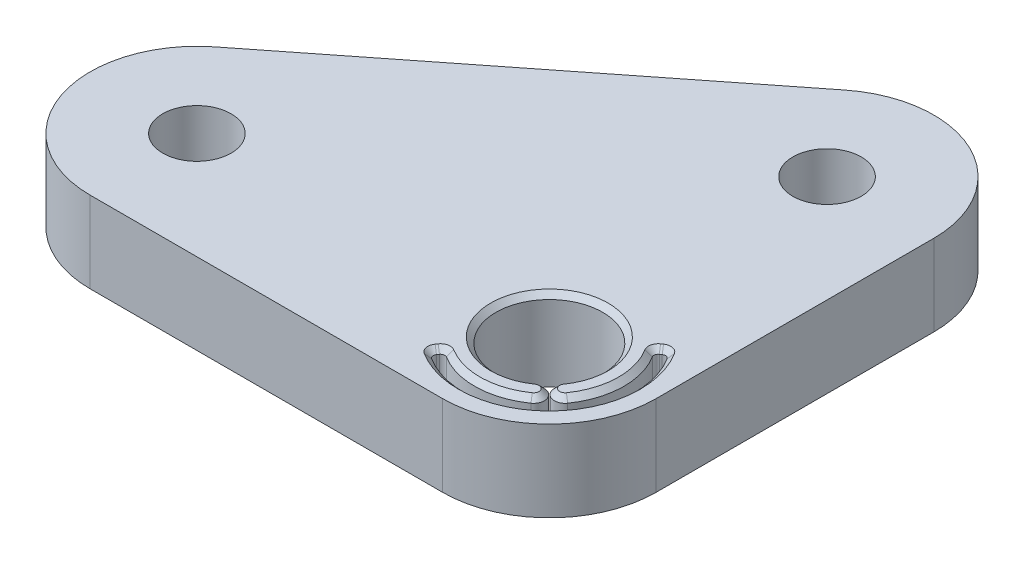
SolidWorks part; units mm, degrees
ref_plane "Front" through (0, 0, 0) normal (0, 0, 1) x (1, 0, 0)
ref_plane "Top" through (0, 0, 0) normal (0, 1, 0) x (1, 0, 0)
ref_plane "Right" through (0, 0, 0) normal (1, 0, 0) x (0, 0, -1)
sketch "Sketch1" plane through (0, 0, 0) normal (0, 1, 0) x (1, 0, 0)
  line L0 (0, 0) -> (16.5, 0) construction
  line L1 (16.5, 0) -> (0, 13) construction
  line L2 (0, 13) -> (0, 0) construction
  line L3 (-5, -5) -> (30.9254, -5)
  line L4 (30.9254, -5) -> (-5, 23.3048)
  line L5 (-5, 23.3048) -> (-5, -5)
  circle A0 centre (16.5, 0) radius 1.6
  circle A1 centre (0, 0) radius 2.5
  circle A2 centre (0, 13) radius 1.6
  dimension "D3" = 5
  dimension "D4" = 3.2
  dimension "D1" = 16.5
  dimension "D2" = 13
  dimension "D5" = 5
extrude "Boss-Extrude1" add sketch "Sketch1" along normal blind 1.57
fillet "Fillet1" radius 5 3 edges at (-5, 0.785, -23.3048) (-5, 0.785, 5) (30.9254, 0.785, 5)
other "Move Face1" [suppressed] offset 0.0762 parameters "D1"=0.0762
sketch "Sketch2" plane through (0, 1.57, 0) normal (0, 1, 0) x (1, 0, 0)
  line L3 (19.5944, 3.9275) -> (3.0944, 16.9275)
  line L4 (-5, 13) -> (-5, 0)
  line L5 (0, -5) -> (16.5, -5)
  line L6 (19.5944, 3.9275) -> (3.0944, 16.9275)
  line L7 (-5, 13) -> (-5, 0)
  line L8 (0, -5) -> (16.5, -5)
  circle A0 centre (0, 0) radius 2.5 construction
  circle A1 centre (16.5, 0) radius 1.6 construction
  circle A2 centre (0, 13) radius 1.6 construction
  arc A3 (3.0944, 16.9275) -> (-5, 13) centre (0, 13) ccw
  arc A4 (-5, 0) -> (0, -5) centre (0, 0) ccw
  arc A5 (16.5, -5) -> (19.5944, 3.9275) centre (16.5, 0) ccw
  arc A6 (3.0944, 16.9275) -> (-5, 13) centre (0, 13) ccw
  arc A7 (-5, 0) -> (0, -5) centre (0, 0) ccw
  arc A8 (16.5, -5) -> (19.5944, 3.9275) centre (16.5, 0) ccw
  circle A9 centre (0, 0) radius 2.5
  circle A10 centre (16.5, 0) radius 1.6
  circle A11 centre (0, 13) radius 1.6
  dimension "D1" = 0
extrude "Boss-Extrude2" add sketch "Sketch2" along normal blind 2.23
sketch "Sketch3" plane through (0, 0, 0) normal (0, -1, 0) x (1, 0, 0)
  circle A0 centre (16.5, 0) radius 3
  circle A1 centre (0, -13) radius 3
  circle A2 centre (0, -13) radius 1.6 construction
  circle A3 centre (16.5, 0) radius 1.6 construction
  circle A4 centre (0, -13) radius 1.6
  circle A5 centre (16.5, 0) radius 1.6
  dimension "D1" = 6
extrude "Boss-Extrude3" add sketch "Sketch3" along normal blind 1
sketch "Sketch4" plane through (0, 3.8, 0) normal (0, 1, 0) x (1, 0, 0)
  line B0 (1.7207, -2.4575) -> (0, 0) construction
  line B1 (2.1191, -3.0264) -> (2.1766, -3.1085)
  line B2 (-3.0264, 2.1191) -> (-3.1085, 2.1766)
  line B3 (-1.7207, -2.4575) -> (0, 0) construction
  arc B4 (2.1187, -3.3928) -> (-3.3928, 2.1187) centre (0, 0) cw
  arc B5 (-1.4339, -2.0479) -> (-2.0075, -2.867) centre (-1.7207, -2.4575) ccw
  arc B6 (-2.0075, -2.867) -> (1.8496, -2.9714) centre (0, 0) ccw
  arc B7 (-2.867, -2.0075) -> (-2.9714, 1.8496) centre (0, 0) cw
  arc B8 (-2.0479, -1.4339) -> (-2.867, -2.0075) centre (-2.4575, -1.7207) cw
  arc B9 (-1.4339, -2.0479) -> (-2.0479, -1.4339) centre (0, 0) cw
  arc B10 (2.1191, -3.0264) -> (1.8496, -2.9714) centre (1.9553, -3.1411) ccw
  arc B11 (2.1766, -3.1085) -> (2.1187, -3.3928) centre (2.0127, -3.2232) cw
  arc B12 (-3.1085, 2.1766) -> (-3.3928, 2.1187) centre (-3.2232, 2.0127) ccw
  arc B13 (-3.0264, 2.1191) -> (-2.9714, 1.8496) centre (-3.1411, 1.9553) cw
sketch_block_instance "5mm_bore_flexure_relief-1"
sketch_block "5mm_bore_flexure_relief" parameters "D4"=2.5, "D6"=0.2, "D1"=80, "D2"=0.5, "D3"=70, "D5"=1
extrude "Cut-Extrude1" cut sketch "Sketch4" against normal blind 10
sketch "Sketch5" plane through (9.4139, 0, -11.9484) normal (0.6189, 0, -0.7855) x (-0.7855, 0, -0.6189)
  line L0 (-12.9606, 0.2) -> (8.0453, 0.2) construction
  line L1 (-12.9606, 3.8) -> (-12.9606, 0) construction
  line L2 (8.0453, 0) -> (8.0453, 3.8) construction
  line L3 (-12.9606, 0) -> (8.0453, 0) construction
  text T0 "RCR-03" font "Century Gothic" height in points 12
  dimension "D1" = 0.2
extrude "Part Num Left" [suppressed] cut sketch "Sketch5" against normal blind 0.4
chamfer "Chamfer1" distance 1 angle 45 2 edges at (0, 0, -10) (16.5, 0, 3)
chamfer "Chamfer2" distance 0.25 angle 45 12 edges at (-2.8284, 3.8, 2.8284) (2.2087, 3.8, 3.2631) (-3.2631, 3.8, -2.2087) (2.1478, 3.8, 3.0674) (-3.0674, 3.8, -2.1478) (1.9953, 3.8, 2.9452) (-2.9452, 3.8, -1.9953) (-0.0946, 3.8, 3.4987) (-3.4987, 3.8, 0.0946) (-2.1303, 3.8, 2.1707) (-2.1707, 3.8, 2.1303) (1.7678, 3.8, -1.7678)
mirror "Mirror1" about plane through (-5, 1.57, -23.3048) normal (1, 0, 0) of bodies 106 104
delete or keep bodies "Body-Delete/Keep 1" type keep bodies bodies 105
sketch "Sketch6" plane through (-13.2439, 0, -16.8096) normal (-0.6189, 0, -0.7855) x (-0.7855, 0, 0.6189)
  line L0 (-0.1904, 0.2) -> (20.8155, 0.2) construction
  line L1 (-0.1904, 0) -> (-0.1904, 3.8) construction
  line L2 (20.8155, 3.8) -> (20.8155, 0) construction
  line L3 (20.8155, 0) -> (-0.1904, 0) construction
  text T0 "RCR-03" font "Century Gothic" height in points 12
  dimension "D1" = 0.2
extrude "Part Num Right" cut sketch "Sketch6" against normal blind 0.4
